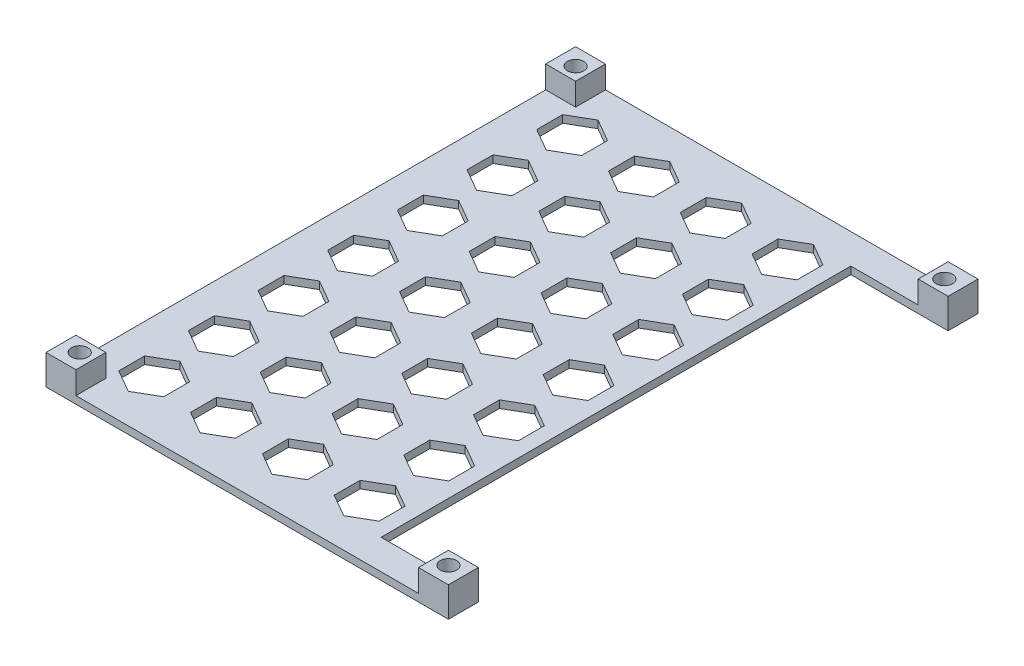
SolidWorks part; units mm, degrees
ref_plane "Front Plane" through (0, 0, 0) normal (0, 0, 1) x (1, 0, 0)
ref_plane "Top Plane" through (0, 0, 0) normal (0, 1, 0) x (1, 0, 0)
ref_plane "Right Plane" through (0, 0, 0) normal (1, 0, 0) x (0, 0, -1)
sketch "Sketch1" plane through (0, 0, 0) normal (0, 1, 0) x (1, 0, 0)
  line L0 (0, 0) -> (53.8, 0)
  line L5 (53.8, 0) -> (53.8, 4)
  line L6 (53.8, 4) -> (40.8, 4)
  line L7 (40.8, 4) -> (40.8, 66.8)
  line L8 (40.8, 66.8) -> (53.8, 66.8)
  line L9 (53.8, 66.8) -> (53.8, 70.8)
  line L10 (53.8, 70.8) -> (0, 70.8)
  line L11 (0, 70.8) -> (0, 0)
  dimension "D1" = 53.8
  dimension "D2" = 13
  dimension "D3" = 70.8
  dimension "D4" = 4
  dimension "D5" = 4
extrude "Boss-Extrude1" add sketch "Sketch1" along normal blind 1
sketch "Sketch2" plane through (0, 1, 0) normal (0, 1, 0) x (1, 0, 0)
  line L0 (40.8, 66.8) -> (0, 66.8) construction
  line L1 (0, 70.8) -> (0, 0) construction
  line L2 (4, 70.8) -> (4, 0) construction
  line L3 (53.8, 70.8) -> (0, 70.8) construction
  line L5 (0, 0) -> (53.8, 0) construction
  line L6 (38.8, 66.8) -> (38.8, 0) construction
  line L7 (40.8, 4) -> (40.8, 66.8) construction
  line L9 (7, 66.8) -> (4, 65.0679)
  line L10 (4, 65.0679) -> (4, 61.6038)
  line L11 (4, 61.6038) -> (7, 59.8718)
  line L12 (7, 59.8718) -> (10, 61.6038)
  line L13 (10, 61.6038) -> (10, 65.0679)
  line L14 (10, 65.0679) -> (7, 66.8)
  circle A0 centre (7, 63.3359) radius 3 construction
  dimension "D1" = 4
  dimension "D2" = 2
  dimension "D3" = 6
extrude "Cut-Extrude1" cut sketch "Sketch2" against normal up to surface (1 mm away) up to face at (37.1, 0, -35.4)
pattern_linear "LPattern1" count 4 spacing 9.6 along (1, 0, 0) count 7 spacing 9.312 along (0, 0, 1) of "Cut-Extrude1"
sketch "Sketch3" plane through (0, 1, 0) normal (0, 1, 0) x (1, 0, 0)
  line L0 (40.8, 66.8) -> (53.8, 66.8) construction
  line L1 (0, 70.8) -> (4, 70.8)
  line L2 (0, 70.8) -> (0, 66.8)
  line L3 (0, 66.8) -> (4, 66.8)
  line L4 (4, 70.8) -> (4, 66.8)
  line L5 (53.8, 70.8) -> (49.8, 70.8)
  line L6 (53.8, 70.8) -> (53.8, 66.8)
  line L7 (53.8, 66.8) -> (49.8, 66.8)
  line L8 (49.8, 70.8) -> (49.8, 66.8)
  line L9 (0, 0) -> (53.8, 0) construction
  line L10 (53.8, 4) -> (49.8, 4)
  line L11 (53.8, 4) -> (53.8, 0)
  line L12 (53.8, 0) -> (49.8, 0)
  line L13 (49.8, 4) -> (49.8, 0)
  line L15 (0, 0) -> (4, 0)
  line L16 (0, 0) -> (0, 4)
  line L17 (0, 4) -> (4, 4)
  line L18 (4, 0) -> (4, 4)
  dimension "D1" = 4
extrude "Boss-Extrude2" add sketch "Sketch3" along normal blind 3
sketch "Sketch4" plane through (0, 4, 0) normal (0, 1, 0) x (1, 0, 0)
  line L3 (0, 68.55) -> (53.8, 68.55) construction
  line L4 (0, 70.8) -> (0, 66.8) construction
  line L5 (53.8, 66.8) -> (53.8, 70.8) construction
  line L6 (4, 70.8) -> (0, 70.8) construction
  circle A0 centre (2.25, 68.55) radius 1.1
  circle A1 centre (51.55, 68.55) radius 1.1
  dimension "D3" = 2.2
  dimension "D1" = 2.25
  dimension "D2" = 2.25
  dimension "D4" = 2.25
extrude "Cut-Extrude2" cut sketch "Sketch4" against normal up to surface (4 mm away) up to face at (16.6, 0, -63.3359)
ref_plane "Plane1" through (0, 0, -35.4) normal (0, 0, -1) x (-1, 0, 0)
mirror "Mirror1" about plane through (0, 0, -35.4) normal (0, 0, -1) of "Cut-Extrude2"
